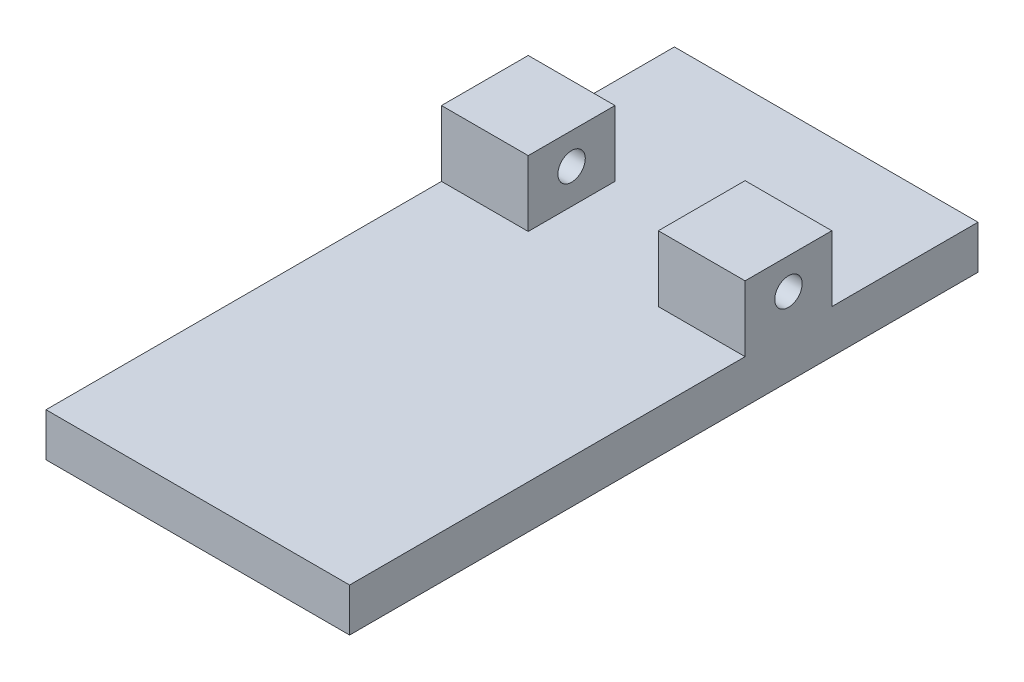
SolidWorks part; units mm, degrees
ref_plane "Front Plane" through (0, 0, 0) normal (0, 0, 1) x (1, 0, 0)
ref_plane "Top Plane" through (0, 0, 0) normal (0, 1, 0) x (1, 0, 0)
ref_plane "Right Plane" through (0, 0, 0) normal (1, 0, 0) x (0, 0, -1)
sketch "Sketch1" plane through (0, 0, 0) normal (0, 1, 0) x (1, 0, 0)
  line L1 (-11.1125, -20.6) -> (11.1125, -20.6)
  line L2 (-11.1125, -20.6) -> (-11.1125, 25.4)
  line L3 (-11.1125, 25.4) -> (11.1125, 25.4)
  line L4 (11.1125, -20.6) -> (11.1125, 25.4)
  dimension "D1" = 11.1125
  dimension "D2" = 25.4
  dimension "D3" = 46
  dimension "D4" = 22.225
extrude "Boss-Extrude1" add sketch "Sketch1" along normal blind 3.175 contours L2 L3 L4 L1
sketch "Sketch2" plane through (0, 3.175, 0) normal (0, 1, 0) x (1, 0, 0)
  line L0 (11.1125, -20.6) -> (11.1125, 25.4) construction
  line L1 (4.7625, 8.35) -> (11.1125, 8.35)
  line L2 (4.7625, 8.35) -> (4.7625, 14.7)
  line L3 (4.7625, 14.7) -> (11.1125, 14.7)
  line L4 (11.1125, 8.35) -> (11.1125, 14.7)
  line L6 (-11.1125, 25.4) -> (11.1125, 25.4) construction
  point P8 (11.1125, 11.525)
  dimension "D1" = 13.875
  dimension "D2" = 6.35
  dimension "D3" = 6.35
extrude "Boss-Extrude2" add sketch "Sketch2" along normal blind 4.8095
hole_wizard "Ø1.0mm Dowel Hole1" positions "Sketch5" profile "Sketch6" hole size "Ø1.0" standard "ANSI Metric" end condition through all
sketch "Sketch5" plane through (4.7625, 0, 0) normal (-1, 0, 0) x (0, 0, 1)
  line L0 (-14.7, 3.175) -> (-8.35, 3.175) construction
  line L1 (-8.35, 7.9845) -> (-8.35, 3.175) construction
  point P0 (-11.525, 5.715)
  dimension "D1" = 2.54
  dimension "D2" = 3.175
sketch "Sketch6" plane through (4.7625, 5.715, -11.525) normal (0, 1, 0) x (0, 0, 1)
  line L0 (0, 0) -> (0, 6.35)
  line L1 (0, 6.35) -> (1.0025, 6.35)
  line L2 (1.0025, 6.35) -> (1.0025, 0)
  line L5 (1.0025, 0) -> (0, 0)
  line L11 (0, -6.35) -> (0, 107.95) construction
  dimension "Thru Hole Dia." = 2.005
  dimension "Thru Hole Depth" = 6.35
ref_axis "Axis1" through (0, 3.175, -25.4) along (0, 0, 1)
ref_plane "Plane1" through (0, 0, 0) normal (-1, 0, 0) x (0, 0, 1)
mirror "Mirror1" about plane through (0, 0, 0) normal (-1, 0, 0) of "Ø1.0mm Dowel Hole1", "Boss-Extrude2"
